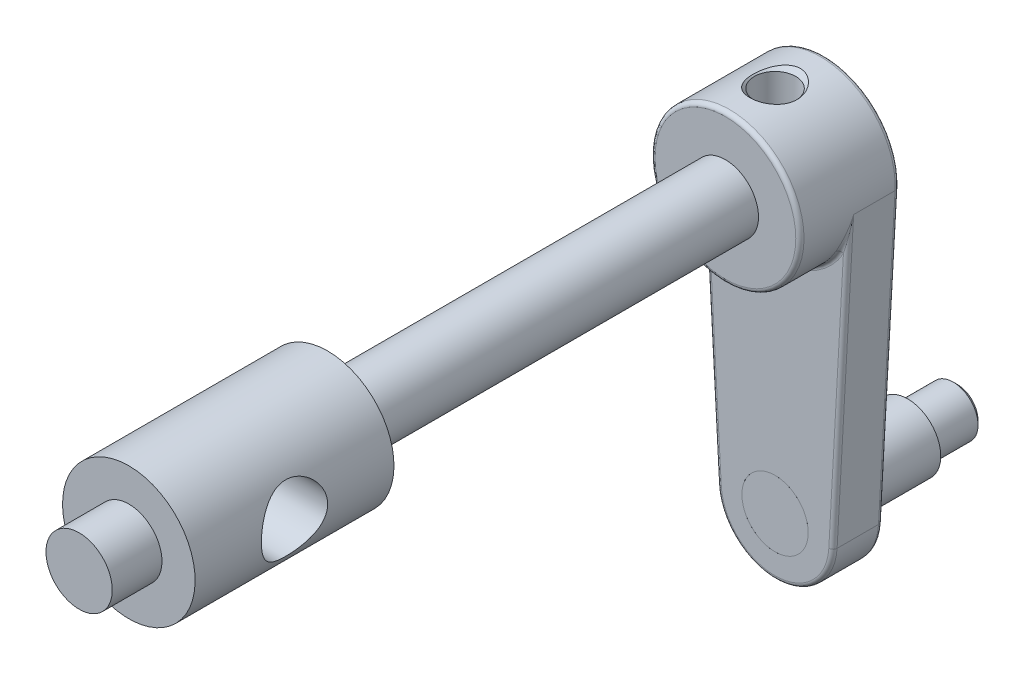
SolidWorks part; units mm, degrees
note: The reader was unsure of these and kept them because the rebuilt part matched: shared geometry of "Sketch1<3>".
ref_plane "Front Plane" through (0, 0, 0) normal (0, 0, 1) x (1, 0, 0)
ref_plane "Top Plane" through (0, 0, 0) normal (0, 1, 0) x (1, 0, 0)
ref_plane "Right Plane" through (0, 0, 0) normal (1, 0, 0) x (0, 0, -1)
sketch "Sketch1" plane through (0, 0, 0) normal (0, 0, 1) x (1, 0, 0)
  line L0 (-4.4931, -0.25) -> (-3.4946, -18.1944)
  line L1 (4.4931, -0.25) -> (3.4946, -18.1944)
  circle A0 centre (0, 0) radius 2
  circle A2 centre (0, -18) radius 2
  arc A3 (-3.4946, -18.1944) -> (3.4946, -18.1944) centre (0, -18) ccw
  circle A4 centre (0, 0) radius 4.5
  dimension "D1" = 4
  dimension "D2" = 9
  dimension "D3" = 4
  dimension "D4" = 7
  dimension "D5" = 18
extrude "Boss-Extrude1" add sketch "Sketch1" along normal blind 3 contours A4 L0 A3 L1 A2
extrude "Boss-Extrude2" add sketch "Sketch1<3>" along normal blind 6 contours A4 A0
sketch "Sketch1<3>" plane through (0, 0, 0) normal (0, 0, 1) x (1, 0, 0) same geometry as "Sketch1"
sketch "Sketch2" plane through (0, 0, 0) normal (1, 0, 0) x (0, 0, -1)
  line L0 (17.5084, 0) -> (-47.0795, 0) construction
  line L1 (0, 0) -> (0, 2)
  line L2 (0, -0.25) -> (0, 4.5) construction
  line L3 (0, 2) -> (-30, 2)
  line L4 (-30, 2) -> (-30, 4)
  line L5 (-30, 4) -> (-42, 4)
  line L6 (-42, 4) -> (-42, 2)
  line L7 (-42, 2) -> (-45, 2)
  line L8 (-45, 2) -> (-45, 0)
  line L9 (0, 0) -> (-45, 0)
  dimension "D1" = 30
  dimension "D2" = 3
  dimension "D3" = 12
  dimension "D4" = 4
  dimension "D5" = 8
revolve "Revolve1" add sketch "Sketch2" angle 360 about L9
sketch "Sketch3" plane through (0, 0, 0) normal (1, 0, 0) x (0, 0, -1)
  circle A0 centre (-36, 0) radius 2
  dimension "D2" = 4
  dimension "D1" = 6
extrude "Cut-Extrude1" cut sketch "Sketch3" against normal through all both and the other way through all
ref_plane "Plane1" through (0, 4.5, 0) normal (0, 1, 0) x (1, 0, 0)
sketch "Sketch5" plane through (0, 4.5, 0) normal (0, 1, 0) x (1, 0, 0)
  point P0 (0, -3)
  dimension "D1" = 3
hole_wizard "M3x0.5 Tapped Hole2" positions "Sketch5" profile "Sketch7" tap size "M3x0.5" standard "ANSI Metric"
sketch "Sketch7" plane through (0, 4.5, 3) normal (1, 0, 0) x (0, 0, 1)
  line L0 (0, 0) -> (0, 3.7511)
  line L1 (0, 3.7511) -> (1.25, 3)
  line L2 (1.25, 3) -> (1.25, 0.275)
  line L3 (1.25, 0.275) -> (1.525, 0)
  line L5 (1.525, 0) -> (0, 0)
  line L6 (-1.25, 0.275) -> (-1.525, 0) construction
  line L10 (0, 3.7511) -> (-1.25, 3) construction
  line L11 (0, -6.35) -> (0, 107.95) construction
  dimension "Tap Drill Dia." = 2.5
  dimension "Tap Drill Depth" = 3
  dimension "Near C'Sink Dia." = 3.05
  dimension "Near C'Sink Angle" = 90
  dimension "Drill Angle" = 118
cosmetic thread "Hole Thread1" parameters "D1"=2.5, "D2"=3
sketch "Sketch9" plane through (0, 0, 0) normal (1, 0, 0) x (0, 0, -1)
  line L0 (-3, -18) -> (-3, -16)
  line L2 (-3, -16) -> (5, -16)
  line L3 (5, -16) -> (5, -16.5)
  line L4 (5, -16.5) -> (8, -16.5)
  line L5 (8, -16.5) -> (8, -18)
  line L6 (8, -18) -> (-3, -18)
  dimension "D1" = 8
  dimension "D2" = 3
  dimension "D3" = 1.5
  dimension "D4" = 2
  dimension "D5" = 18
revolve "Revolve2" add sketch "Sketch9" angle 360 about L6
cosmetic thread "Cosmetic Thread1" parameters "D2"=2.439
fillet "Fillet1" radius 0.25 9 edges at (3.9938, -9.2222, 0) (3.9938, -9.2222, 3) (0, -21.5, 0) (0, -21.5, 3) (-3.9938, -9.2222, 0) (-3.9938, -9.2222, 3) (0, -4.5, 3) (0, 4.5, 0) (4.5, 0, 6)
chamfer "Chamfer1" distance 0.25 angle 45 1 edges at (-1.5, -18, -8)
